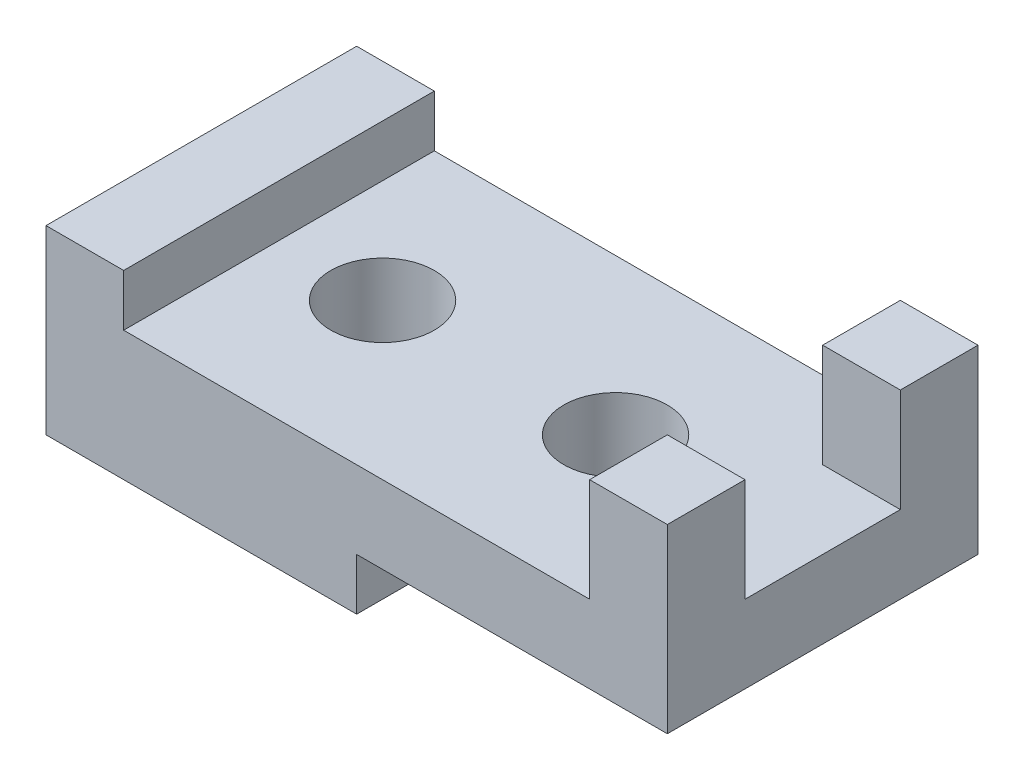
SolidWorks part; units mm, degrees
ref_plane "Front Plane" through (0, 0, 0) normal (0, 0, 1) x (1, 0, 0)
ref_plane "Top Plane" through (0, 0, 0) normal (0, 1, 0) x (1, 0, 0)
ref_plane "Right Plane" through (0, 0, 0) normal (1, 0, 0) x (0, 0, -1)
sketch "Sketch1" plane through (0, 0, 0) normal (0, 0, 1) x (1, 0, 0)
  line L0 (0, 36.5193) -> (0, -33.4807) construction
  line L1 (-61.3344, 0) -> (181.3344, 0) construction
  line L2 (-60, 7.5) -> (-60, -27.5)
  line L3 (-60, -27.5) -> (0, -27.5)
  line L4 (0, -27.5) -> (0, -17.5)
  line L5 (0, -17.5) -> (60, -17.5)
  line L6 (60, -17.5) -> (60, 17.5)
  line L7 (60, 17.5) -> (45, 17.5)
  line L8 (45, 17.5) -> (45, -2.5)
  line L9 (45, -2.5) -> (-45, -2.5)
  line L10 (-45, -2.5) -> (-45, 7.5)
  line L11 (-45, 7.5) -> (-60, 7.5)
  point P16 (60, 0)
  dimension "D1" = 35
  dimension "D2" = 60
  dimension "D3" = 120
  dimension "D4" = 10
  dimension "D5" = 10
  dimension "D6" = 15
  dimension "D7" = 15
  dimension "D8" = 20
  dimension "D9" = 35
  dimension "D10" = 90
extrude "Boss-Extrude1" add sketch "Sketch1" against normal blind 60
sketch "Sketch2" plane through (0, -2.5, 0) normal (0, 1, 0) x (1, 0, 0)
  line L0 (-45, 60) -> (-45, 0) construction
  line L2 (45, 60) -> (-45, 60) construction
  circle A0 centre (-25, 30) radius 10
  circle A1 centre (20, 30) radius 10
  dimension "D3" = 20
  dimension "D4" = 20
  dimension "D1" = 20
  dimension "D2" = 30
  dimension "D5" = 45
  dimension "D6" = 30
extrude "Cut-Extrude1" cut sketch "Sketch2" against normal through all
sketch "Sketch3" plane through (60, 0, 0) normal (1, 0, 0) x (0, 0, -1)
  line L15 (15, 17.5) -> (15, -2.5)
  line L16 (60, 17.5) -> (0, 17.5) construction
  line L17 (15, -2.5) -> (45, -2.5)
  line L18 (45, -2.5) -> (45, 17.5)
  line L19 (45, 17.5) -> (15, 17.5)
  line L20 (60, -17.5) -> (0, -17.5) construction
  point P8 (30, -17.5)
  point P9 (30, -2.5)
  dimension "D1" = 20
  dimension "D2" = 30
extrude "Cut-Extrude2" cut sketch "Sketch3" against normal blind 15
